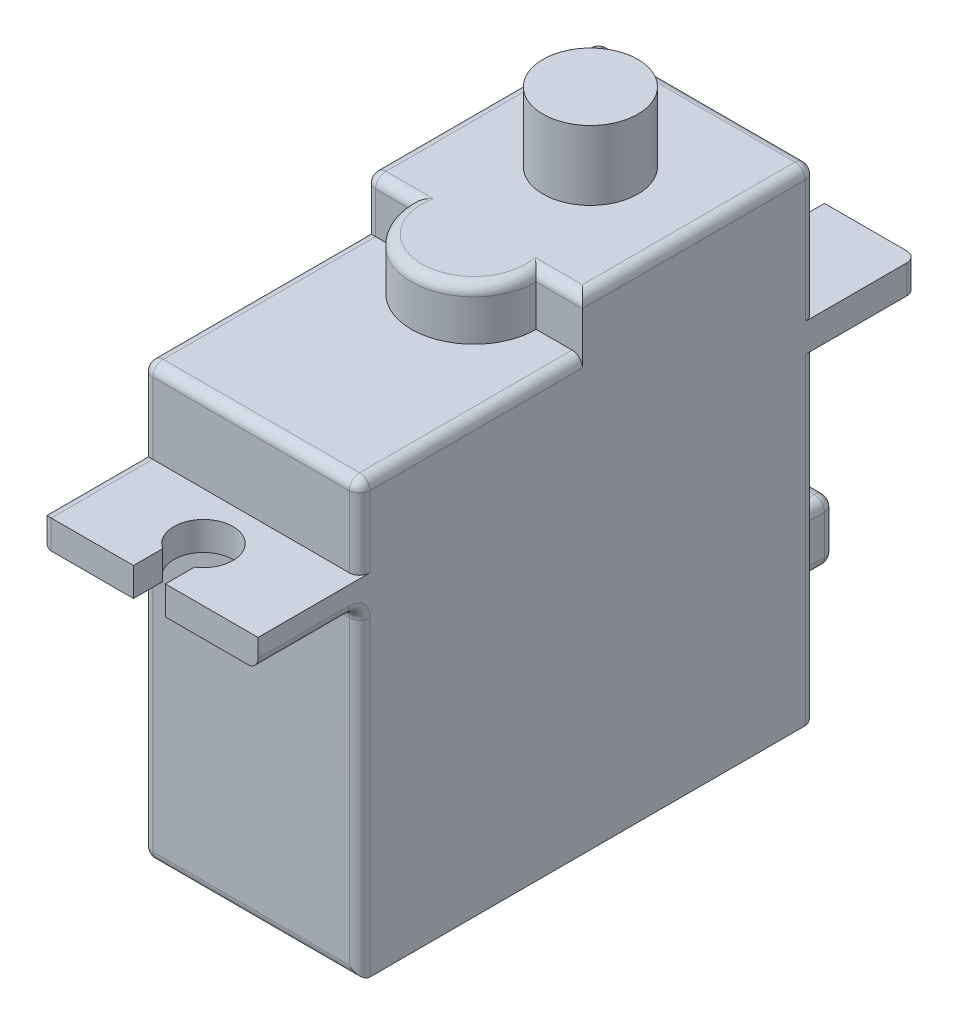
SolidWorks part; units mm, degrees
ref_plane "Front" through (0, 0, 0) normal (0, 0, 1) x (1, 0, 0)
ref_plane "Top" through (0, 0, 0) normal (0, 1, 0) x (1, 0, 0)
ref_plane "Right" through (0, 0, 0) normal (1, 0, 0) x (0, 0, -1)
sketch "Base Sketch" plane through (0, 0, 0) normal (0, 1, 0) x (1, 0, 0)
  line L1 (0, 0) -> (13.3096, 0)
  line L2 (0, 0) -> (0, 27.94)
  line L3 (0, 27.94) -> (13.3096, 27.94)
  line L4 (13.3096, 0) -> (13.3096, 27.94)
  dimension "D1" = 27.94
  dimension "D2" = 13.3096
extrude "Base" add sketch "Base Sketch" along normal blind 19.6977
sketch "Mounting Point Sketch" plane through (0, 19.6977, 0) normal (0, 1, 0) x (1, 0, 0)
  line L0 (0, 34.163) -> (0, -6.223)
  line L1 (13.3096, -6.223) -> (13.3096, 34.163)
  line L2 (13.3096, 0) -> (13.3096, 27.94) construction
  line L3 (0, 27.94) -> (0, 0) construction
  line L4 (0, -6.223) -> (0, 0) construction
  line L5 (13.3096, 0) -> (13.3096, 27.94) construction
  line L6 (0, 27.94) -> (0, 0) construction
  line L7 (0, 34.163) -> (13.3096, 34.163)
  line L8 (0, -6.223) -> (13.3096, -6.223)
  point P8 (13.3096, 13.97)
  point P12 (0, 13.97)
  dimension "D1" = 40.386
extrude "Mounting Point" add sketch "Mounting Point Sketch" along normal blind 1.7526
sketch "Mounting Holes Sketch" plane through (0, 21.4503, 0) normal (0, 1, 0) x (1, 0, 0)
  line L0 (6.6548, 32.6644) -> (6.6548, 32.3774) construction
  line L1 (13.3096, 34.163) -> (0, 34.163) construction
  line L2 (0, -6.223) -> (13.3096, -6.223) construction
  line L3 (0, 13.97) -> (13.3096, 13.97) construction
  line L4 (0, 34.163) -> (0, -6.223) construction
  line L5 (13.3096, -6.223) -> (13.3096, 34.163) construction
  line L6 (6.6548, 29.0449) -> (6.6548, -6.223) construction
  line L7 (5.6769, 34.163) -> (7.6327, 34.163)
  line L8 (5.6769, 34.163) -> (5.6769, 32.3774)
  line L10 (7.6327, 34.163) -> (7.6327, 32.3774)
  line L11 (5.6769, -6.223) -> (7.6327, -6.223)
  line L12 (5.6769, -6.223) -> (5.6769, -4.4374)
  line L13 (7.6327, -6.223) -> (7.6327, -4.4374)
  arc A0 (5.6769, 32.3774) -> (7.6327, 32.3774) centre (6.6548, 30.8546) ccw
  arc A1 (5.6769, -4.4374) -> (7.6327, -4.4374) centre (6.6548, -2.9146) cw
  point P15 (6.6548, 32.6644)
  point P19 (0, 0)
  dimension "D1" = 3.6195
  dimension "D2" = 1.7856
  dimension "D3" = 1.9558
extrude "Mounting Holes" cut sketch "Mounting Holes Sketch" against normal through all
sketch "Middle Sketch" plane through (0, 21.4503, 0) normal (0, 1, 0) x (1, 0, 0)
  line L4 (0, 0) -> (13.3096, 0)
  line L5 (13.3096, 0) -> (13.3096, 27.94)
  line L6 (13.3096, 27.94) -> (0, 27.94)
  line L7 (0, 27.94) -> (0, 0)
  line L8 (0, 0) -> (13.3096, 0)
  line L9 (13.3096, 0) -> (13.3096, 27.94)
  line L10 (5.6769, 32.3774) -> (5.6769, 34.163)
  line L11 (5.6769, 34.163) -> (0, 34.163)
  line L12 (0, 34.163) -> (0, -6.223)
  line L13 (0, -6.223) -> (5.6769, -6.223)
  line L14 (5.6769, -6.223) -> (5.6769, -4.4374)
  line L15 (7.6327, -4.4374) -> (7.6327, -6.223)
  line L16 (7.6327, -6.223) -> (13.3096, -6.223)
  line L17 (13.3096, -6.223) -> (13.3096, 34.163)
  line L18 (13.3096, 34.163) -> (7.6327, 34.163)
  line L19 (7.6327, 34.163) -> (7.6327, 32.3774)
  line L20 (5.6769, 32.3774) -> (5.6769, 34.163)
  line L21 (5.6769, 34.163) -> (0, 34.163)
  line L22 (0, 34.163) -> (0, -6.223)
  line L23 (0, -6.223) -> (5.6769, -6.223)
  line L24 (5.6769, -6.223) -> (5.6769, -4.4374)
  line L25 (7.6327, -4.4374) -> (7.6327, -6.223)
  line L26 (7.6327, -6.223) -> (13.3096, -6.223)
  line L27 (13.3096, -6.223) -> (13.3096, 34.163)
  line L28 (13.3096, 34.163) -> (7.6327, 34.163)
  line L29 (7.6327, 34.163) -> (7.6327, 32.3774)
  line L30 (13.3096, 27.94) -> (0, 27.94)
  line L31 (0, 27.94) -> (0, 0)
  arc A2 (7.6327, -4.4374) -> (5.6769, -4.4374) centre (6.6548, -2.9146) ccw
  arc A3 (5.6769, 32.3774) -> (7.6327, 32.3774) centre (6.6548, 30.8546) ccw
  arc A4 (7.6327, -4.4374) -> (5.6769, -4.4374) centre (6.6548, -2.9146) ccw
  arc A5 (5.6769, 32.3774) -> (7.6327, 32.3774) centre (6.6548, 30.8546) ccw
  line M25 (13.3096, -6.223) -> (13.3096, 34.163)
  dimension "D1" = 0
  dimension "D2" = 0
extrude "Middle" add sketch "Middle Sketch" along normal blind 4.9911 contours L30 L22 L8 M25 region at (6.6548, 21.4503, -13.97)
sketch "Top Sketch" plane through (0, 26.4414, 0) normal (0, 1, 0) x (1, 0, 0)
  line L0 (13.3096, 0) -> (13.3096, 27.94) construction
  line L1 (0, 27.94) -> (13.3096, 27.94)
  line L2 (0, 27.94) -> (0, 13.6525)
  line L3 (0, 13.6525) -> (2.8321, 13.6525)
  line L4 (13.3096, 27.94) -> (13.3096, 13.6525)
  line L5 (10.4775, 13.6525) -> (13.3096, 13.6525)
  arc A0 (2.8321, 13.6525) -> (10.4775, 13.6525) centre (6.6548, 13.6525) ccw
  dimension "D2" = 7.6454
  dimension "D1" = 14.2875
  dimension "D3" = 7.6454
  dimension "D4" = 6.6548
extrude "Top extrude" add sketch "Top Sketch" along normal blind 3.1496
sketch "Gear Sketch" plane through (0, 29.591, 0) normal (0, 1, 0) x (1, 0, 0)
  line L0 (0, 13.6525) -> (2.8321, 13.6525) construction
  line L1 (10.4775, 13.6525) -> (13.3096, 13.6525) construction
  line L2 (13.3096, 13.6525) -> (13.3096, 27.94) construction
  line L3 (0, 27.94) -> (0, 13.6525) construction
  line L4 (13.3096, 27.94) -> (0, 27.94) construction
  line L5 (0, 13.6525) -> (2.8321, 13.6525) construction
  line L6 (10.4775, 13.6525) -> (13.3096, 13.6525) construction
  line L7 (13.3096, 13.6525) -> (13.3096, 27.94) construction
  line L8 (0, 27.94) -> (0, 13.6525) construction
  line L9 (13.3096, 27.94) -> (0, 27.94) construction
  line L10 (0, 13.6525) -> (13.3096, 13.6525) construction
  line L11 (6.6548, 27.94) -> (6.6548, 13.6525) construction
  line L12 (0, 20.7963) -> (13.3096, 20.7963) construction
  circle A0 centre (6.6548, 20.7963) radius 2.9083
  dimension "D1" = 5.8166
extrude "Gear" add sketch "Gear Sketch" along normal blind 4.2418
sketch "Servo Cable Sketch" plane through (0, 0, -27.94) normal (0, 0, -1) x (-1, 0, 0)
  line L0 (-13.3096, 0) -> (0, 0) construction
  line L1 (-3.9751, 7.3914) -> (-9.3345, 7.3914)
  line L2 (-3.9751, 7.3914) -> (-3.9751, 3.7338)
  line L3 (-3.9751, 3.7338) -> (-9.3345, 3.7338)
  line L4 (-9.3345, 7.3914) -> (-9.3345, 3.7338)
  line L5 (0, 19.6977) -> (0, 0) construction
  line L6 (0, 3.7338) -> (-13.3096, 3.7338) construction
  line L7 (-13.3096, 19.6977) -> (-13.3096, 0) construction
  point P12 (-6.6548, 3.7338)
  dimension "D1" = 3.7338
  dimension "D2" = 3.9751
  dimension "D3" = 3.6576
extrude "Sevo Cable" add sketch "Servo Cable Sketch" along normal blind 5.1562
fillet "Fillet1" radius 0.635 38 edges at (13.3096, 19.6977, 3.1115) (0, 9.8488, -27.94) (0, 19.6977, -31.0515) (0, 20.574, -34.163) (0, 21.4503, -31.0515) (0, 25.5206, -27.94) (0, 29.591, -20.7963) (0, 28.0162, -13.6525) (0, 26.4414, -6.8263) (0, 23.9458, 0) (0, 21.4503, 3.1115) (0, 20.574, 6.223) (0, 19.6977, 3.1115) (0, 0, -13.97) (0, 9.8488, 0) (6.6548, 19.6977, 0) (13.3096, 9.8488, 0) (6.6548, 0, 0) (9.3345, 5.5626, -33.0962) (6.6548, 3.7338, -33.0962) (3.9751, 5.5626, -33.0962) (6.6548, 7.3914, -33.0962) (3.9751, 7.3914, -30.5181) (3.9751, 3.7338, -30.5181) (9.3345, 3.7338, -30.5181) (9.3345, 7.3914, -30.5181) (6.6548, 0, -27.94) (13.3096, 9.8488, -27.94) (13.3096, 29.591, -20.7963) (13.3096, 23.9458, 0) (6.6548, 26.4414, 0) (13.3096, 26.4414, -6.8263) (11.8935, 29.591, -13.6525) (1.4161, 29.591, -13.6525) (6.6548, 29.591, -9.8298) (6.6548, 29.591, -27.94) (13.3096, 25.5206, -27.94) (13.3096, 20.574, -34.163)
